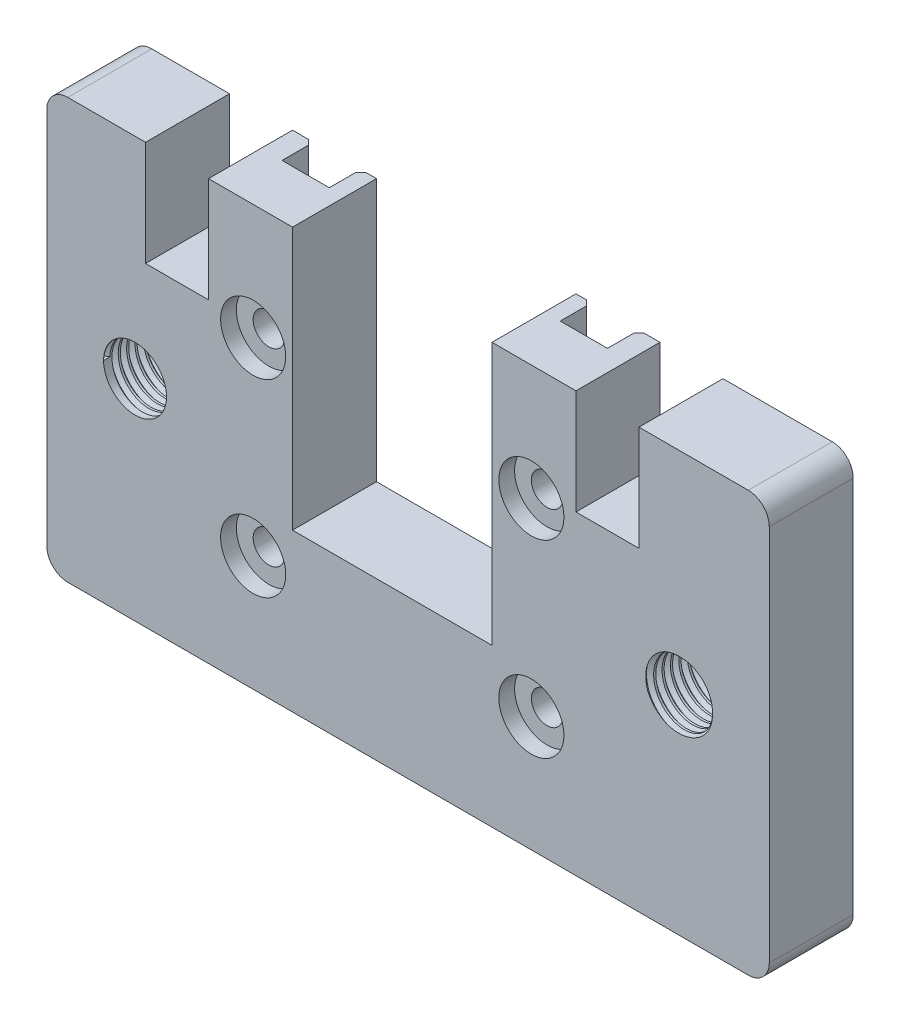
SolidWorks part; units mm, degrees
ref_plane "前视基准面" through (0, 0, 0) normal (0, 0, 1) x (1, 0, 0)
ref_plane "上视基准面" through (0, 0, 0) normal (0, 1, 0) x (1, 0, 0)
ref_plane "右视基准面" through (0, 0, 0) normal (1, 0, 0) x (0, 0, -1)
sketch "草图1" plane through (0, 0, 0) normal (0, 0, 1) x (1, 0, 0)
  line L0 (0, 0) -> (26, 0) construction
  line L1 (0, 0) -> (-26, 0) construction
  line L2 (-22.2669, 20) -> (22.2669, 20)
  line L3 (-22.2669, -20) -> (22.2669, -20)
  line L5 (22.2669, 20) -> (34.4093, 20)
  line L7 (22.2669, -20) -> (34.4093, -20)
  line L8 (34.4093, 20) -> (34.4093, -20)
  line L9 (-22.2669, 20) -> (-34.4093, 20)
  line L11 (-22.2669, -20) -> (-34.4093, -20)
  line L12 (-34.4093, 20) -> (-34.4093, -20)
  circle A2 centre (-26, 0) radius 3
  circle A3 centre (26, 0) radius 3
  point P13 (-26, -20)
  point P16 (28, -20)
  point P21 (-26, 20)
  dimension "D3" = 20
  dimension "D5" = 6
  dimension "D6" = 6
  dimension "D1" = 26
  dimension "25" = 26
extrude "凸台-拉伸1" add sketch "草图1" against normal blind 8
sketch "草图2" plane through (0, 0, 0) normal (0, 0, 1) x (1, 0, 0)
  line L0 (-12.5, 20) -> (-12.5, -20)
  line L1 (-34.4093, 20) -> (34.4093, 20) construction
  line L2 (34.4093, -20) -> (-34.4093, -20) construction
  line L6 (9.5, 20) -> (9.5, -20)
  line L10 (9.5, 20) -> (14, 20)
  line L11 (34.4093, 20) -> (-34.4093, 20) construction
  line L12 (14, 20) -> (14, -20)
  line L13 (-34.4093, -20) -> (34.4093, -20) construction
  line L14 (14, -20) -> (9.5, -20)
  line L15 (-12.5, -20) -> (-17, -20)
  line L16 (-17, -20) -> (-17, 20)
  line L17 (-17, 20) -> (-12.5, 20)
  dimension "D1" = 12.5
  dimension "D2" = 4.5
  dimension "D3" = 9.5
  dimension "D4" = 4.5
extrude "切除-拉伸1" cut sketch "草图2" along normal blind 3 from surface starting at face at (29, 0, -8)
chamfer "倒角1" distance 0.5 angle 45 4 edges at (14, 0, -8) (-17, 0, -8) (9.5, 0, -8) (-12.5, 0, -8)
sketch "草图3" plane through (0, 0, -5) normal (0, 0, -1) x (-1, 0, 0)
  line L1 (-9.5, -20) -> (-9.5, 20) construction
  line L3 (12.5, 20) -> (12.5, -20) construction
  circle A0 centre (-11.75, 9) radius 1.5
  circle A1 centre (14.75, 9) radius 1.5
  circle A3 centre (-11.75, -9) radius 1.5
  circle A4 centre (14.75, -9) radius 1.5
  dimension "D1" = 9
  dimension "D3" = 9
  dimension "D4" = 3
  dimension "D5" = 3
  dimension "D6" = 3
  dimension "D7" = 3
  dimension "D8" = 2.25
  dimension "D9" = 2.25
  dimension "D10" = 2.25
  dimension "D2" = 9
  dimension "D11" = 2.25
extrude "切除-拉伸2" cut sketch "草图3" against normal blind 10
fillet "圆角1" radius 2 4 edges at (-34.4093, 20, -4) (-34.4093, -20, -4) (34.4093, -20, -4) (34.4093, 20, -4)
sketch "草图5" plane through (0, 0, 0) normal (0, 0, 1) x (1, 0, 0)
  circle A0 centre (-14.75, 9) radius 3.1
  circle A1 centre (11.75, 9) radius 3.1
  circle A2 centre (11.75, -9) radius 3.1
  circle A3 centre (-14.75, -9) radius 3.1
  dimension "D1" = 6.2
  dimension "D2" = 6.2
  dimension "D3" = 6.2
  dimension "D4" = 6.2
extrude "切除-拉伸3" cut sketch "草图5" against normal blind 1.5
sketch "草图6" plane through (0, 0, -8) normal (0, 0, -1) x (-1, 0, 0)
  line L0 (-9, 20) -> (12, 20) construction
  line L1 (-8, 20) -> (11, 20)
  line L2 (-8, 20) -> (-8, -5)
  line L3 (-8, -5) -> (11, -5)
  line L4 (11, 20) -> (11, -5)
  line L7 (-9.5, -20) -> (-9.5, 20) construction
  line L8 (12.5, 20) -> (12.5, -20) construction
  dimension "D1" = 1.5
  dimension "D2" = 1.5
  dimension "D3" = 25
extrude "切除-拉伸4" cut sketch "草图6" against normal blind 10 contours L3 L4 L1 L2
sketch "草图7" plane through (0, 0, -8) normal (0, 0, -1) x (-1, 0, 0)
  line L0 (-32.4093, 20) -> (-14.5, 20) construction
  line L1 (-16, 20) -> (-22, 20)
  line L2 (-16, 20) -> (-16, 10)
  line L3 (-16, 10) -> (-22, 10)
  line L4 (-22, 20) -> (-22, 10)
  line L5 (-14, 20) -> (-14, -20) construction
  line L6 (17.5, 20) -> (32.4093, 20) construction
  line L7 (19, 20) -> (25, 20)
  line L8 (19, 20) -> (19, 10)
  line L9 (19, 10) -> (25, 10)
  line L10 (25, 20) -> (25, 10)
  line L11 (17, -20) -> (17, 20) construction
  dimension "D1" = 2
  dimension "D2" = 6
  dimension "D3" = 10
  dimension "D4" = 2
  dimension "D5" = 6
  dimension "D6" = 10
  dimension "D7" = 19
  dimension "D8" = 16
extrude "切除-拉伸5" cut sketch "草图7" against normal blind 10
thread "螺纹线1" pitch 0.8 method cut profile "螺纹线轮廓1" start angle 0, offset 0, length 0, pitch 0.8, diameter 6
ref_plane "基准面1" through (-29, 0, 0) normal (0, -1, 0) x (-1, 0, 0)
sketch "螺纹线轮廓1" plane through (-29, 0, 0) normal (0, -1, 0) x (-1, 0, 0)
  line L0 (0, 0) -> (0, 0.8) construction
  line L1 (0, 0) -> (0.433, 0.25)
  line L2 (0.433, 0.25) -> (0.433, 0.35)
  line L3 (0.433, 0.35) -> (0, 0.6)
  line L4 (0.433, 0.3) -> (0, 0.3) construction
  line L11 (0, 0) -> (0, 0.6)
  point P2 (0, 0)
  dimension "Pitch" = 0.8
  dimension "Profile_Angle" = 60
  dimension "Profile_Land" = 0.1
  dimension "Profile_Height" = 0.433
thread "螺纹线2" pitch 0.8 method cut profile "螺纹线轮廓2" start angle 0, offset 0, length 0, pitch 0.8, diameter 6
ref_plane "基准面2" through (29, 0, -8) normal (0, -1, 0) x (1, 0, 0)
sketch "螺纹线轮廓2" plane through (29, 0, -8) normal (0, -1, 0) x (1, 0, 0)
  line L0 (0, 0) -> (0, 0.8) construction
  line L1 (0, 0) -> (0.433, 0.25)
  line L2 (0.433, 0.25) -> (0.433, 0.35)
  line L3 (0.433, 0.35) -> (0, 0.6)
  line L4 (0.433, 0.3) -> (0, 0.3) construction
  line L11 (0, 0) -> (0, 0.6)
  point P2 (0, 0)
  dimension "Pitch" = 0.8
  dimension "Profile_Angle" = 60
  dimension "Profile_Land" = 0.1
  dimension "Profile_Height" = 0.433
